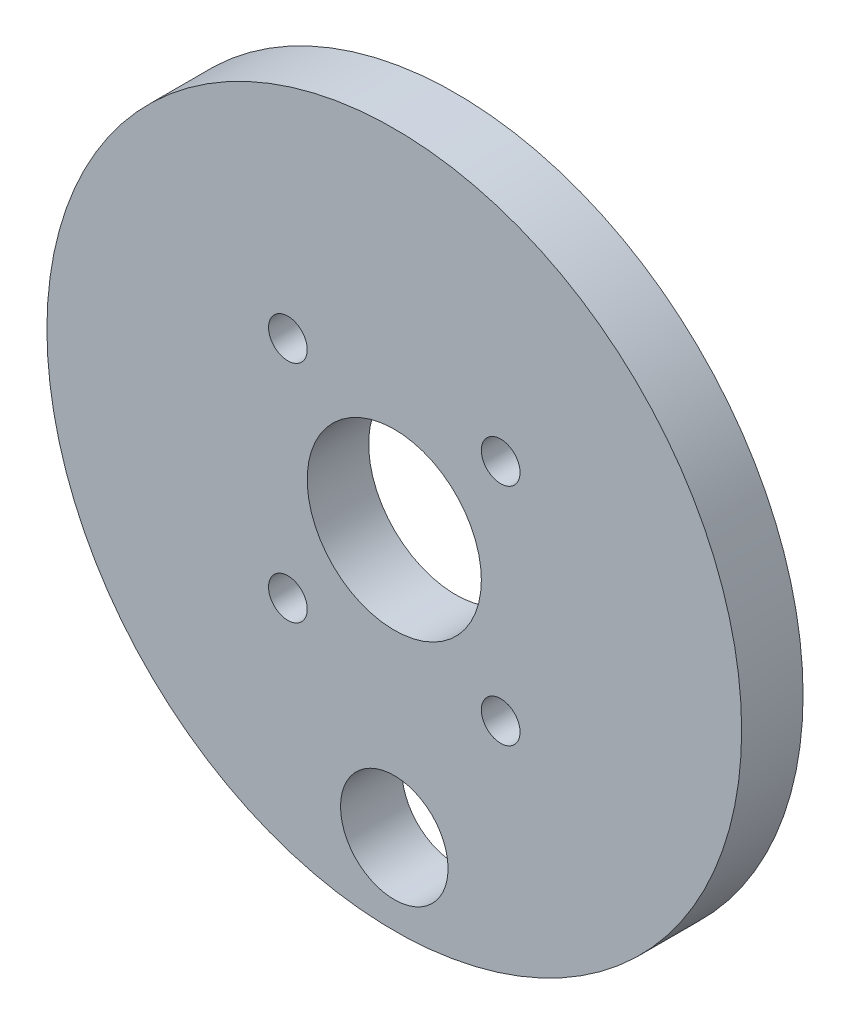
SolidWorks part; units mm, degrees
ref_plane "Front Plane" through (0, 0, 0) normal (0, 0, 1) x (1, 0, 0)
ref_plane "Top Plane" through (0, 0, 0) normal (0, 1, 0) x (1, 0, 0)
ref_plane "Right Plane" through (0, 0, 0) normal (1, 0, 0) x (0, 0, -1)
sketch "Sketch1" plane through (0, 0, 0) normal (0, 0, 1) x (1, 0, 0)
  circle A0 centre (0, 0) radius 35.91
  circle A1 centre (0, 0) radius 9
  dimension "D1" = 71.82
  dimension "D2" = 18
extrude "Boss-Extrude1" add sketch "Sketch1" along normal blind 6.35
sketch "Sketch2" plane through (0, 0, 0) normal (0, 0, -1) x (-1, 0, 0)
  circle A0 centre (-11, 11.619) radius 2
  circle A1 centre (11, 11.619) radius 2
  circle A2 centre (11, -11.619) radius 2
  circle A3 centre (-11, -11.619) radius 2
  point P0 (-11, 11.619)
  point P1 (11, 11.619)
  point P3 (11, -11.619)
  point P5 (-11, -11.619)
extrude "Cut-Extrude1" cut sketch "Sketch2" against normal through all
sketch "Sketch3" plane through (0, 0, 0) normal (0, 0, -1) x (-1, 0, 0)
  circle A0 centre (0, -27.5594) radius 5.5563
  dimension "D1" = 11.1125
extrude "Cut-Extrude2" cut sketch "Sketch3" against normal through all
